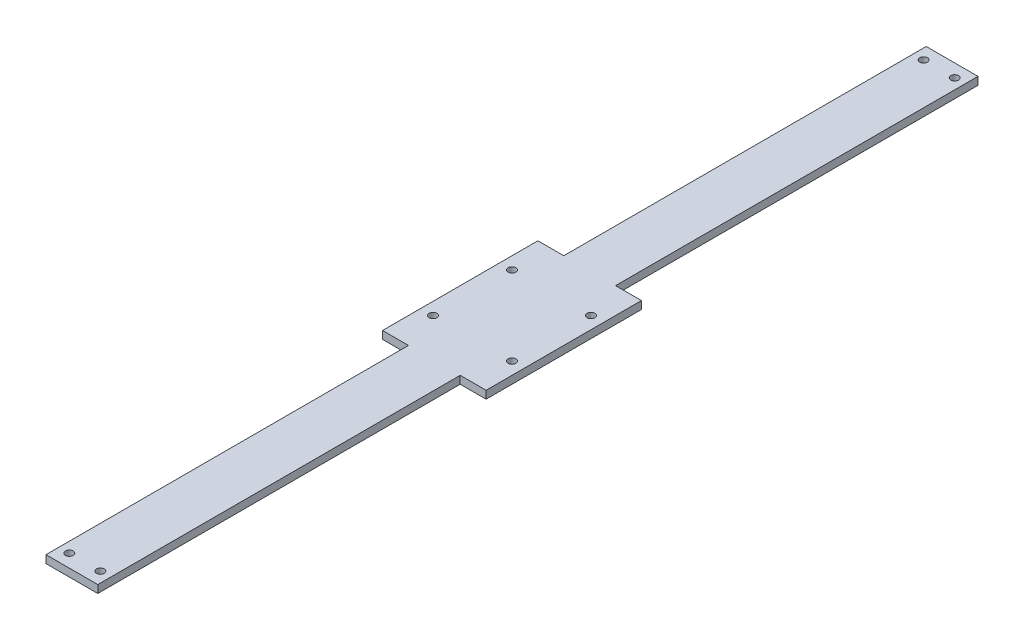
SolidWorks part; units mm, degrees
ref_plane "Front Plane" through (0, 0, 0) normal (0, 0, 1) x (1, 0, 0)
ref_plane "Top Plane" through (0, 0, 0) normal (0, 1, 0) x (1, 0, 0)
ref_plane "Right Plane" through (0, 0, 0) normal (1, 0, 0) x (0, 0, -1)
sketch "Sketch1" plane through (0, 0, 0) normal (0, 1, 0) x (1, 0, 0)
  line L0 (-10, 170) -> (-10, 30)
  line L1 (-15.25, 15.25) -> (15.25, 15.25) construction
  line L2 (-15.25, 15.25) -> (-15.25, -15.25) construction
  line L3 (-15.25, -15.25) -> (15.25, -15.25) construction
  line L4 (15.25, 15.25) -> (15.25, -15.25) construction
  line L5 (-15.25, 15.25) -> (15.25, -15.25) construction
  line L6 (-15.25, -15.25) -> (15.25, 15.25) construction
  line L7 (-20, 170) -> (20, 170) construction
  line L8 (-20, 170) -> (-20, -170) construction
  line L9 (-20, -170) -> (20, -170) construction
  line L10 (20, 170) -> (20, -170) construction
  line L11 (-10, 30) -> (-20, 30)
  line L12 (0, 170) -> (0, -170) construction
  line L13 (-20, 0) -> (20, 0) construction
  line L14 (10, 30) -> (20, 30)
  line L15 (10, 170) -> (10, 30)
  line L16 (10, -30) -> (20, -30)
  line L17 (10, -170) -> (10, -30)
  line L18 (-10, -30) -> (-20, -30)
  line L19 (-10, -170) -> (-10, -30)
  line L20 (-10, -170) -> (10, -170)
  line L21 (20, 30) -> (20, -30)
  line L22 (-20, 30) -> (-20, -30)
  line L23 (-10, 170) -> (10, 170)
  circle A0 centre (-15.25, 15.25) radius 1.5
  circle A1 centre (15.25, 15.25) radius 1.5
  circle A2 centre (15.25, -15.25) radius 1.5
  circle A3 centre (-15.25, -15.25) radius 1.5
  point P0 (0, 0)
  point P14 (0, 170)
  point P15 (-20, 0)
  dimension "D2" = 3
  dimension "D1" = 30.5
  dimension "D3" = 340
  dimension "D4" = 40
  dimension "D5" = 10
  dimension "D6" = 60
extrude "Boss-Extrude1" add sketch "Sketch1" along normal mid plane 3
sketch "Sketch2" plane through (0, 0, 0) normal (0, 1, 0) x (1, 0, 0)
  circle A0 centre (-6, 165) radius 1.5 construction
  circle A1 centre (6, 165) radius 1.5 construction
  circle A2 centre (-6, 165) radius 1.5
  circle A3 centre (6, 165) radius 1.5
extrude "connector0hole" cut sketch "Sketch2" against normal through all both and the other way through all
ref_axis "Axis1" through (0, 177.4955, 0) along (0, -1, 0)
pattern_circular "CirPattern1" count 2 over 360 about axis through (0, 177.4955, 0) along (0, -1, 0) of "connector0hole"
